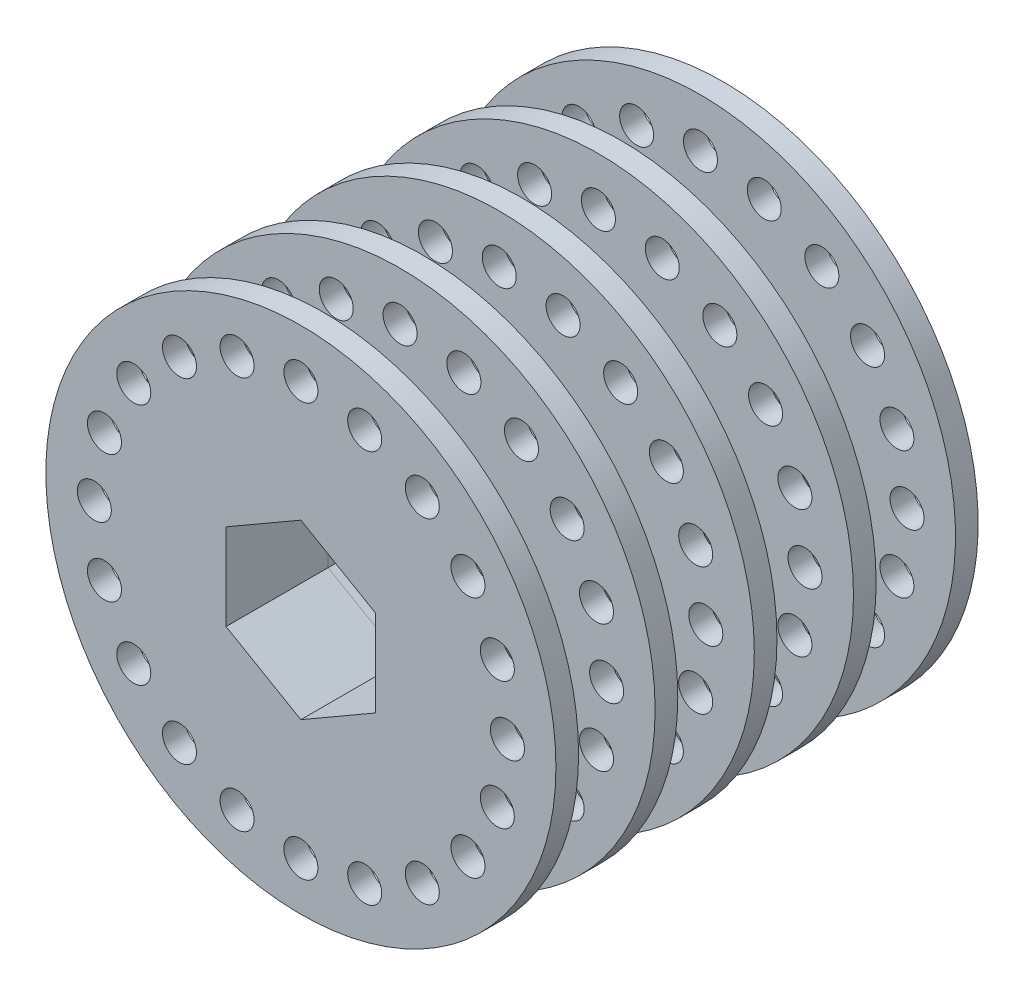
SolidWorks part; units mm, degrees
ref_plane "Front Plane" through (0, 0, 0) normal (0, 0, 1) x (1, 0, 0)
ref_plane "Top Plane" through (0, 0, 0) normal (0, 1, 0) x (1, 0, 0)
ref_plane "Right Plane" through (0, 0, 0) normal (1, 0, 0) x (0, 0, -1)
sketch "Sketch1" plane through (0, 0, 0) normal (0, 0, 1) x (1, 0, 0)
  circle A0 centre (0, 0) radius 10.16
  circle A1 centre (0, 0) radius 22.5
  circle A2 centre (0, 18.2218) radius 1.5
  circle A3 centre (5.6309, 17.33) radius 1.5
  circle A4 centre (10.7105, 14.7418) radius 1.5
  circle A5 centre (14.7418, 10.7105) radius 1.5
  circle A6 centre (17.33, 5.6309) radius 1.5
  circle A7 centre (18.2218, 0) radius 1.5
  circle A8 centre (17.33, -5.6309) radius 1.5
  circle A9 centre (14.7418, -10.7105) radius 1.5
  circle A10 centre (10.7105, -14.7418) radius 1.5
  circle A11 centre (5.6309, -17.33) radius 1.5
  circle A12 centre (0, -18.2218) radius 1.5
  circle A13 centre (-5.6309, -17.33) radius 1.5
  circle A14 centre (-10.7105, -14.7418) radius 1.5
  circle A15 centre (-14.7418, -10.7105) radius 1.5
  circle A16 centre (-17.33, -5.6309) radius 1.5
  circle A17 centre (-18.2218, 0) radius 1.5
  circle A18 centre (-17.33, 5.6309) radius 1.5
  circle A19 centre (-14.7418, 10.7105) radius 1.5
  circle A20 centre (-10.7105, 14.7418) radius 1.5
  circle A21 centre (-5.6309, 17.33) radius 1.5
  point P47 (0, 0)
  dimension "D1" = 20.32
  dimension "D2" = 45
  dimension "D3" = 3
  dimension "D4" = 20
extrude "Boss-Extrude1" add sketch "Sketch1" along normal blind 2 contours A0 | A1 A21 A20 A19 A18 A17 A16 A15 A14 A13 A12 A11 A10 A9 A8 A7 A6 A5 A4 A3 A2 A0 region at (0, 0, 0) region at (-21.8636, 0, 0)
extrude "Boss-Extrude2" add sketch "Sketch1<3>" against normal blind 7 contours A0 region at (0, 0, 0)
sketch "Sketch1<3>" plane through (0, 0, 0) normal (0, 0, 1) x (1, 0, 0) same geometry as "Sketch1"
pattern_linear "LPattern2" count 4 spacing 8.75 along (0, 0, -1) of "Boss-Extrude2", "Boss-Extrude1"
sketch "Sketch2" plane through (0, 0, -33.25) normal (0, 0, -1) x (-1, 0, 0)
  circle A1 centre (0, 0) radius 10.16 construction
  circle A2 centre (0, 0) radius 22.5 construction
  circle A3 centre (0, 0) radius 10.16
  circle A4 centre (0, 0) radius 22.5
  circle A5 centre (10.7105, 14.7418) radius 1.5
  circle A6 centre (10.7105, 14.7418) radius 1.5
  circle A7 centre (14.7418, 10.7105) radius 1.5
  circle A8 centre (14.7418, 10.7105) radius 1.5
  circle A9 centre (17.33, 5.6309) radius 1.5
  circle A10 centre (17.33, 5.6309) radius 1.5
  circle A11 centre (18.2218, 0) radius 1.5
  circle A12 centre (18.2218, 0) radius 1.5
  circle A13 centre (17.33, -5.6309) radius 1.5
  circle A14 centre (17.33, -5.6309) radius 1.5
  circle A15 centre (14.7418, -10.7105) radius 1.5
  circle A16 centre (14.7418, -10.7105) radius 1.5
  circle A17 centre (10.7105, -14.7418) radius 1.5
  circle A18 centre (10.7105, -14.7418) radius 1.5
  circle A19 centre (5.6309, -17.33) radius 1.5
  circle A20 centre (5.6309, -17.33) radius 1.5
  circle A21 centre (0, -18.2218) radius 1.5
  circle A22 centre (0, -18.2218) radius 1.5
  circle A23 centre (-5.6309, -17.33) radius 1.5
  circle A24 centre (-5.6309, -17.33) radius 1.5
  circle A25 centre (-10.7105, -14.7418) radius 1.5
  circle A26 centre (-10.7105, -14.7418) radius 1.5
  circle A27 centre (-14.7418, -10.7105) radius 1.5
  circle A28 centre (-14.7418, -10.7105) radius 1.5
  circle A29 centre (-17.33, -5.6309) radius 1.5
  circle A30 centre (-17.33, -5.6309) radius 1.5
  circle A31 centre (-18.2218, 0) radius 1.5
  circle A32 centre (-18.2218, 0) radius 1.5
  circle A33 centre (-17.33, 5.6309) radius 1.5
  circle A34 centre (-17.33, 5.6309) radius 1.5
  circle A35 centre (-14.7418, 10.7105) radius 1.5
  circle A36 centre (-14.7418, 10.7105) radius 1.5
  circle A37 centre (-10.7105, 14.7418) radius 1.5
  circle A38 centre (-10.7105, 14.7418) radius 1.5
  circle A39 centre (-5.6309, 17.33) radius 1.5
  circle A40 centre (-5.6309, 17.33) radius 1.5
  circle A41 centre (0, 18.2218) radius 1.5
  circle A42 centre (0, 18.2218) radius 1.5
  circle A43 centre (0, 0) radius 10.16
  circle A44 centre (0, 0) radius 10.16
  circle A45 centre (5.6309, 17.33) radius 1.5
  circle A46 centre (5.6309, 17.33) radius 1.5
  circle M22 centre (0, 0) radius 10.16
  dimension "D1" = 0
  dimension "D2" = 0
  dimension "D3" = 0
  dimension "D4" = 0
  dimension "D5" = 0
  dimension "D6" = 0
  dimension "D7" = 0
  dimension "D8" = 0
  dimension "D9" = 0
  dimension "D10" = 0
  dimension "D11" = 0
  dimension "D12" = 0
  dimension "D13" = 0
  dimension "D14" = 0
  dimension "D15" = 0
  dimension "D16" = 0
  dimension "D17" = 0
  dimension "D18" = 0
  dimension "D19" = 0
  dimension "D20" = 0
  dimension "D21" = 0
extrude "Boss-Extrude3" add sketch "Sketch2" along normal blind 2 contours A4 A46 A42 A40 A38 A36 A34 A32 A30 A28 A26 A24 A22 A20 A18 A16 A14 A12 A10 A8 A6 M22 | M22 region at (0, 0, -33.25) region at (21.8636, 0, -33.25)
sketch "Sketch3" plane through (0, 0, -35.25) normal (0, 0, -1) x (-1, 0, 0)
  line L1 (0, 7.621) -> (-6.6, 3.8105)
  line L2 (-6.6, 3.8105) -> (-6.6, -3.8105)
  line L3 (-6.6, -3.8105) -> (0, -7.621)
  line L4 (0, -7.621) -> (6.6, -3.8105)
  line L5 (6.6, -3.8105) -> (6.6, 3.8105)
  line L6 (6.6, 3.8105) -> (0, 7.621)
  circle A0 centre (0, 0) radius 6.6 construction
  circle A2 centre (0, 0) radius 19.05
  dimension "D2" = 38.1
extrude "Cut-Extrude1" cut sketch "Sketch3" against normal through all contours L5 L6 L1 L2 L3 L4 region at (0, 0, -35.25)
ref_plane "Plane1" through (0, 0, -3.375) normal (0, 0, -1) x (-1, 0, 0)
ref_plane "Plane2" through (0, 0, -12.125) normal (0, 0, -1) x (-1, 0, 0)
